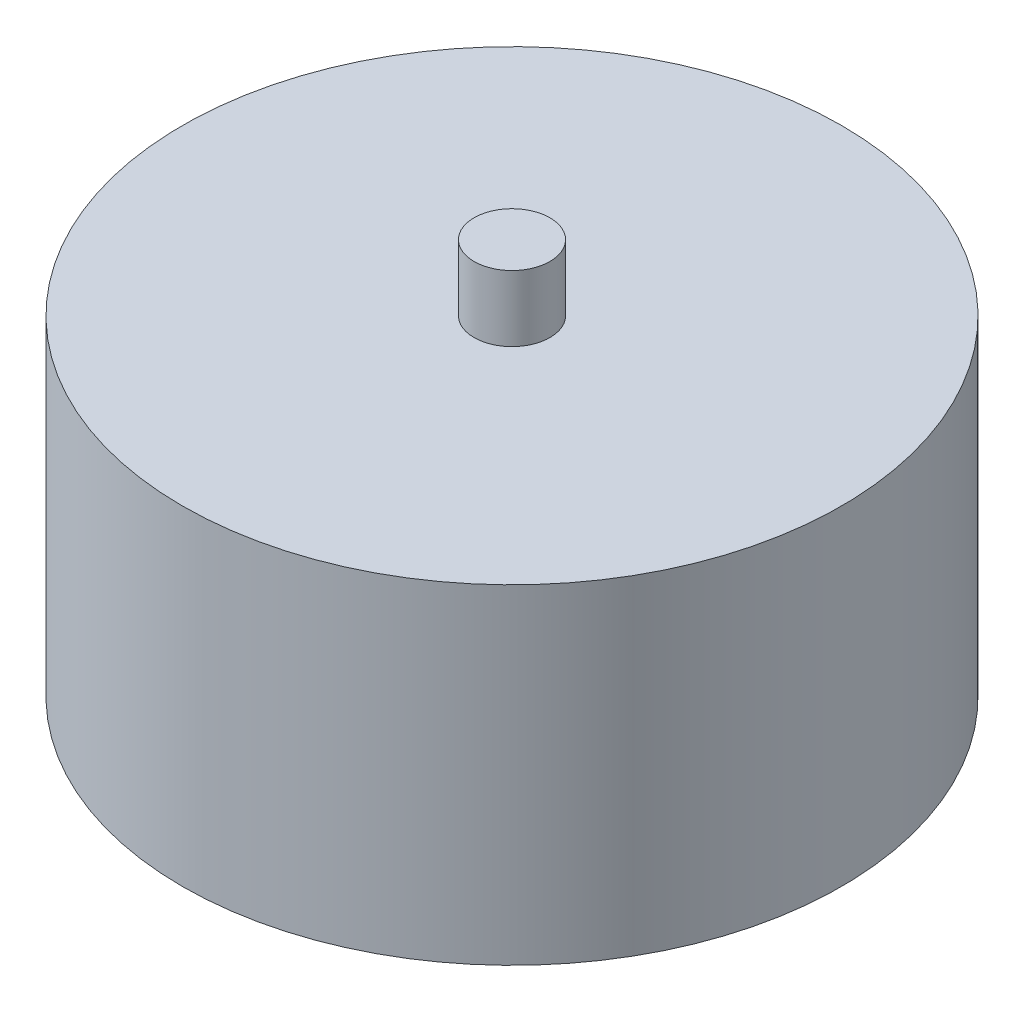
SolidWorks part; units mm, degrees
ref_plane "Front Plane" through (0, 0, 0) normal (0, 0, 1) x (1, 0, 0)
ref_plane "Top Plane" through (0, 0, 0) normal (0, 1, 0) x (1, 0, 0)
ref_plane "Right Plane" through (0, 0, 0) normal (1, 0, 0) x (0, 0, -1)
sketch "Sketch1" plane through (0, 0, 0) normal (0, 1, 0) x (1, 0, 0)
  circle A0 centre (0, 0) radius 10
  circle A1 centre (0, 0) radius 7.5 construction
  circle A2 centre (0, 7.5) radius 1.5
  circle A3 centre (6.4952, -3.75) radius 1.5
  circle A4 centre (-6.4952, -3.75) radius 1.5
  circle A5 centre (0, 0) radius 1.15
  point P12 (0, 0)
  dimension "D1" = 20
  dimension "D3" = 3
  dimension "D4" = 2.3
  dimension "D5" = 15
  dimension "D2" = 3
extrude "Boss-Extrude1" add sketch "Sketch1" against normal blind 10 contours A0
extrude "Boss-Extrude2" add sketch "Sketch1<3>" along normal blind 2 contours A5
sketch "Sketch1<3>" plane through (0, 0, 0) normal (0, 1, 0) x (1, 0, 0) same geometry as "Sketch1"
extrude "Cut-Extrude1" cut sketch "Sketch1<4>" along normal blind 5 from surface contours A3 | A4 | A2 region at (6.4952, 0, 3.75) starting at face at (0, -10, 10)
sketch "Sketch1<4>" plane through (0, 0, 0) normal (0, 1, 0) x (1, 0, 0) same geometry as "Sketch1"
